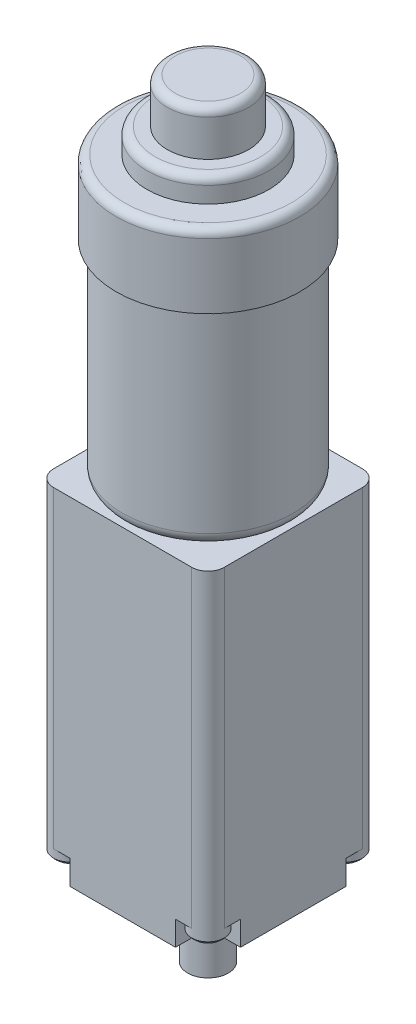
SolidWorks part; units mm, degrees
material "Stop 1060"
ref_plane "Front Plane" through (0, 0, 0) normal (0, 0, 1) x (1, 0, 0)
ref_plane "Top Plane" through (0, 0, 0) normal (0, 1, 0) x (1, 0, 0)
ref_plane "Right Plane" through (0, 0, 0) normal (1, 0, 0) x (0, 0, -1)
sketch "Sketch2" plane through (0, 0, 0) normal (0, 0, 1) x (1, 0, 0)
  line L0 (51.9161, 6.3887) -> (33.9161, 6.3887)
  line L1 (54.9161, 9.3887) -> (54.9161, 57.3887)
  line L2 (46.9161, 81.3887) -> (43.9161, 81.3887)
  line L3 (48.9161, 79.3887) -> (48.9161, 75.3887)
  line L4 (33.9161, 6.3887) -> (33.9161, 92.3887)
  line L6 (56.5161, 57.3887) -> (54.9161, 57.3887)
  line L7 (54.5161, 75.3887) -> (48.9161, 75.3887)
  line L8 (56.5161, 73.3887) -> (56.5161, 57.3887)
  line L12 (33.9161, 92.3887) -> (41.9161, 92.3887)
  line L13 (43.9161, 90.3887) -> (43.9161, 81.3887)
  line L15 (33.9161, 106.8072) -> (33.9161, -9.4217) construction
  arc A0 (51.9161, 6.3887) -> (54.9161, 9.3887) centre (51.9161, 9.3887) ccw
  arc A3 (48.9161, 79.3887) -> (46.9161, 81.3887) centre (46.9161, 79.3887) ccw
  arc A5 (56.5161, 73.3887) -> (54.5161, 75.3887) centre (54.5161, 73.3887) ccw
  arc A7 (43.9161, 90.3887) -> (41.9161, 92.3887) centre (41.9161, 90.3887) ccw
revolve "Revolve1" add sketch "Sketch2" angle 360 about L15
sketch "Sketch3" plane through (0, 6.3887, 0) normal (0, -1, 0) x (1, 0, 0)
  line L0 (33.9161, -18) -> (33.9161, 18) construction
  line L1 (51.9161, 0) -> (15.9161, 0) construction
  line L7 (12.9161, 21) -> (54.9161, 21)
  line L8 (12.9161, 21) -> (12.9161, -21)
  line L9 (12.9161, -21) -> (54.9161, -21)
  line L10 (54.9161, 21) -> (54.9161, -21)
  circle A9 centre (33.9161, 0) radius 18 construction
  dimension "D1" = 21
  dimension "D2" = 42
  dimension "D3" = 21
  dimension "D4" = 42
extrude "Boss-Extrude1" add sketch "Sketch3" along normal blind 77
fillet "Fillet1" radius 4 4 edges at (12.9161, -32.1113, -21) (54.9161, -32.1113, -21) (12.9161, -32.1113, 21) (54.9161, -32.1113, 21)
sketch "Sketch4" plane through (0, -70.6113, 0) normal (0, -1, 0) x (1, 0, 0)
  line L0 (20.9161, -21) -> (46.9161, -21)
  line L1 (54.9161, -13) -> (54.9161, 13)
  line L2 (46.9161, 21) -> (20.9161, 21)
  line L3 (12.9161, 13) -> (12.9161, -13)
  line L4 (16.9161, 13) -> (12.9161, 13)
  line L5 (20.9161, 17) -> (20.9161, 21)
  line L6 (16.9161, -13) -> (12.9161, -13)
  line L7 (20.9161, -17) -> (20.9161, -21)
  line L8 (50.9161, 13) -> (54.9161, 13)
  line L9 (46.9161, 17) -> (46.9161, 21)
  line L10 (50.9161, -13) -> (54.9161, -13)
  line L11 (46.9161, -17) -> (46.9161, -21)
  line L12 (33.9161, -17) -> (33.9161, 17) construction
  line L13 (16.9161, 0) -> (50.9161, 0) construction
  line L14 (33.9161, 21) -> (33.9161, -21) construction
  line L15 (50.9161, 21) -> (16.9161, 21) construction
  line L16 (16.9161, -21) -> (50.9161, -21) construction
  circle A0 centre (16.9161, 0) radius 2
  circle A1 centre (50.9161, 0) radius 2
  circle A2 centre (33.9161, -17) radius 2
  circle A3 centre (33.9161, 17) radius 2
  arc A4 (16.9161, 13) -> (20.9161, 17) centre (16.9161, 17) ccw
  arc A5 (20.9161, -17) -> (16.9161, -13) centre (16.9161, -17) ccw
  arc A6 (46.9161, 17) -> (50.9161, 13) centre (50.9161, 17) ccw
  arc A7 (50.9161, -13) -> (46.9161, -17) centre (50.9161, -17) ccw
  circle A14 centre (33.9161, 0) radius 17 construction
extrude "Boss-Extrude2" add sketch "Sketch4" along normal blind 6
sketch "Sketch5" plane through (0, -76.6113, 0) normal (0, -1, 0) x (1, 0, 0)
  circle A12 centre (33.9161, 0) radius 12.5
extrude "Boss-Extrude3" add sketch "Sketch5" along normal blind 2
sketch "Sketch6" plane through (0, -78.6113, 0) normal (0, -1, 0) x (1, 0, 0)
  line L0 (33.9161, 12.5) -> (33.9161, -12.5) construction
  circle A0 centre (33.9161, 0) radius 12.5 construction
  circle A1 centre (33.9161, 0) radius 12.5 construction
  circle A15 centre (33.9161, 0) radius 5
extrude "Boss-Extrude4" add sketch "Sketch6" along normal blind 18
sketch "Sketch7" plane through (0, -96.6113, 0) normal (0, -1, 0) x (1, 0, 0)
  line L0 (30.7161, 3.8419) -> (30.7161, -3.8419)
  arc A0 (30.7161, 3.8419) -> (30.7161, -3.8419) centre (33.9161, 0) ccw
  dimension "D2" = 10
  dimension "D1" = 3.2
extrude "Cut-Extrude1" cut sketch "Sketch7" against normal blind 14
sketch "Sketch8" plane through (0, 0, 21) normal (0, 0, 1) x (1, 0, 0)
  line L0 (12.9161, -70.6113) -> (12.9161, -72.6113)
  line L1 (16.9161, -67.89) -> (16.9161, -75.7448) construction
  line L2 (16.9161, 6.3887) -> (16.9161, -70.6113) construction
  line L3 (16.9161, -76.6113) -> (16.9161, -70.6113) construction
  line L4 (16.9161, -70.6113) -> (16.9161, -74.6113)
  line L5 (12.9161, -70.6113) -> (16.9161, -70.6113)
  arc A1 (12.9161, -72.6113) -> (16.9161, -74.6113) centre (16.9161, -69.6113) ccw
ref_plane "Plane1" through (0, 0, 17) normal (0, 0, 1) x (1, 0, 0)
sketch "Sketch10" plane through (0, 0, 17) normal (0, 0, 1) x (1, 0, 0)
  line L0 (12.9161, -70.6113) -> (12.9161, -72.6113)
  line L1 (16.9161, -67.89) -> (16.9161, -75.7448) construction
  line L2 (16.9161, -70.6113) -> (16.9161, -74.6113)
  line L3 (12.9161, -70.6113) -> (16.9161, -70.6113)
  line L4 (20.9161, -70.6113) -> (12.9161, -70.6113) construction
  arc A0 (12.9161, -72.6113) -> (16.9161, -74.6113) centre (16.9161, -69.6113) ccw
revolve "Revolve4" add sketch "Sketch10" angle 360 about L1
ref_plane "Plane2" through (0, 0, 0) normal (0, 0, -1) x (-1, 0, 0)
mirror "Mirror1" about plane through (0, 0, 0) normal (0, 0, -1) of "Revolve4"
ref_plane "Plane3" through (33.9161, 0, 0) normal (1, 0, 0) x (0, 0, -1)
mirror "Mirror2" about plane through (33.9161, 0, 0) normal (1, 0, 0) of "Mirror1"
